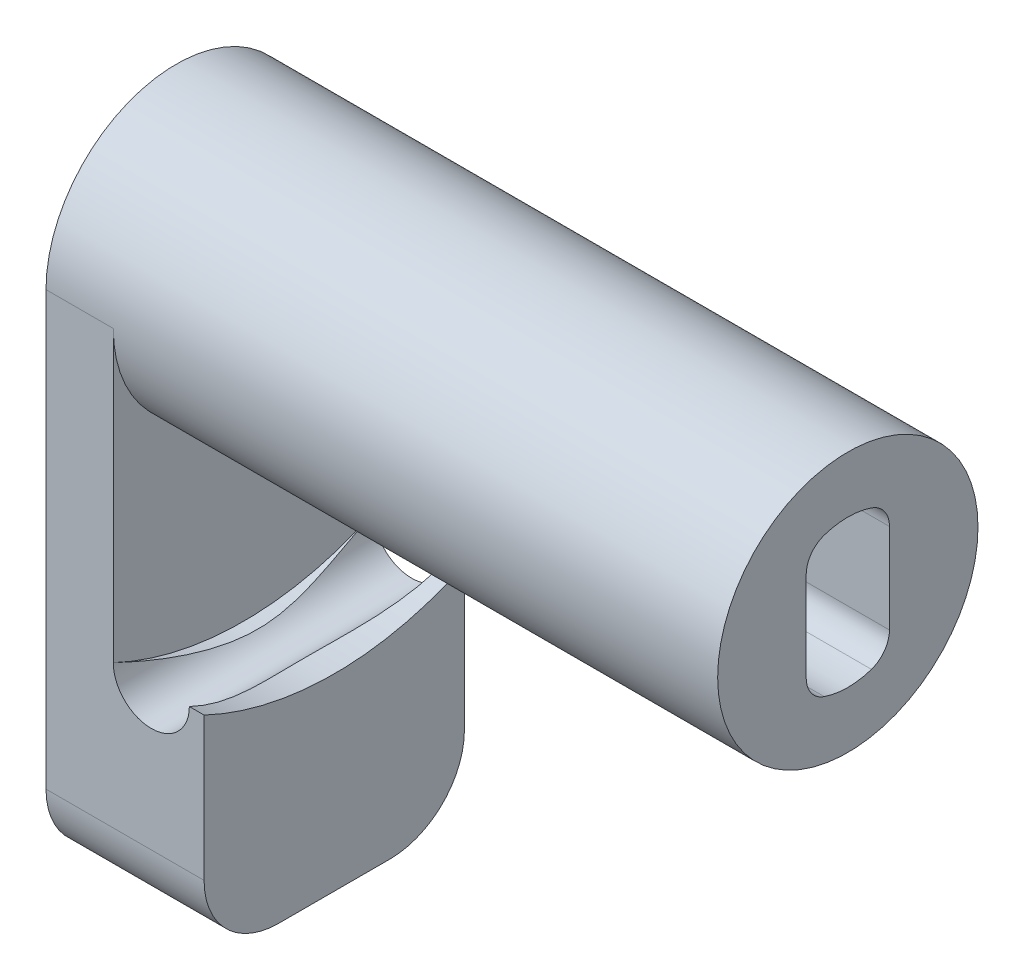
SolidWorks part; units mm, degrees
material "ABS"
ref_plane "Front Plane" through (0, 0, 0) normal (1, 0, 0) x (0, 1, 0)
ref_plane "Top Plane" through (0, 0, 0) normal (0, 0, 1) x (0, 1, 0)
ref_plane "Right Plane" through (0, 0, 0) normal (0, 1, 0) x (-1, 0, 0)
sketch "Sketch1" plane through (0, 0, 0) normal (1, 0, 0) x (0, 1, 0)
  circle A2 centre (0, 0) radius 8.7376
  dimension "D3" = 17.4752
extrude "Boss-Extrude1" add sketch "Sketch1" along normal blind 45.085 contours A2 region at (0, 0, 0)
sketch "Sketch10" plane through (0, 0, 0) normal (-1, 0, 0) x (0, -1, 0)
  line L0 (0, 8.7376) -> (34.036, 8.7376)
  line L2 (34.036, 8.7376) -> (34.036, -8.7376)
  line L3 (34.036, -8.7376) -> (0, -8.7376)
  circle A0 centre (0, 0) radius 8.7376 construction
  arc A2 (0, 8.7376) -> (0, -8.7376) centre (0, 0) cw
  point P2 (34.036, 0)
  dimension "D1" = 34.036
extrude "Boss-Extrude3" add sketch "Sketch10" against normal blind 4.516 contours L0 A2 L3 L2 region at (0, -20.3793, 0)
fillet "Fillet2" radius 5 2 edges at (2.258, -34.036, 8.7376) (2.258, -34.036, -8.7376)
sketch "Sketch14" [suppressed] plane through (0, 0, 0) normal (-1, 0, 0) x (0, 0, 1)
  line L0 (0.5115, -3.4237) -> (0.3944, -4.0089)
  line L1 (0, 0) -> (0, -4.064) construction
  line L2 (0, 0) -> (0.5606, -3.4335) construction
  line L3 (0.6039, -3.4087) -> (0.9011, -3.9262)
  line L4 (-0.6903, -3.3922) -> (-1.0005, -3.9021)
  line L5 (-0.5983, -3.4096) -> (-0.4961, -3.9976)
  line L6 (-1.8089, -2.9515) -> (-2.2748, -3.3245)
  line L7 (-1.7284, -2.9994) -> (-1.8334, -3.5869)
  line L8 (-2.7093, -2.1549) -> (-3.2746, -2.346)
  line L9 (-2.65, -2.2273) -> (-2.9496, -2.7435)
  line L10 (-3.2829, -1.0983) -> (-3.8795, -1.0846)
  line L11 (-3.252, -1.1867) -> (-3.7101, -1.5692)
  line L12 (-3.4605, 0.0907) -> (-4.0165, 0.3077)
  line L13 (-3.4617, -0.0029) -> (-4.023, -0.2057)
  line L14 (-3.2208, 1.2689) -> (-3.669, 1.6629)
  line L15 (-3.2539, 1.1813) -> (-3.8507, 1.1827)
  line L16 (-2.5926, 2.2939) -> (-2.879, 2.8175)
  line L17 (-2.6537, 2.223) -> (-3.214, 2.4284)
  line L18 (-1.6517, 3.0423) -> (-1.7417, 3.6323)
  line L19 (-1.7333, 2.9965) -> (-2.1896, 3.3812)
  line L20 (-0.5115, 3.4237) -> (-0.3944, 4.0089)
  line L21 (-0.6039, 3.4087) -> (-0.9011, 3.9262)
  line L22 (0.6903, 3.3922) -> (1.0005, 3.9021)
  line L23 (0.5983, 3.4096) -> (0.4961, 3.9976)
  line L24 (1.8089, 2.9515) -> (2.2748, 3.3245)
  line L25 (1.7284, 2.9994) -> (1.8334, 3.5869)
  line L26 (2.7093, 2.1549) -> (3.2746, 2.346)
  line L27 (2.65, 2.2273) -> (2.9496, 2.7435)
  line L28 (3.2829, 1.0983) -> (3.8795, 1.0846)
  line L29 (3.252, 1.1867) -> (3.7101, 1.5692)
  line L30 (3.4605, -0.0907) -> (4.0165, -0.3077)
  line L31 (3.4617, 0.0029) -> (4.023, 0.2057)
  line L32 (3.2208, -1.2689) -> (3.669, -1.6629)
  line L33 (3.2539, -1.1813) -> (3.8507, -1.1827)
  line L34 (2.5926, -2.2939) -> (2.879, -2.8175)
  line L35 (2.6537, -2.223) -> (3.214, -2.4284)
  line L36 (1.6517, -3.0423) -> (1.7417, -3.6323)
  line L37 (1.7333, -2.9965) -> (2.1896, -3.3812)
  line L38 (-0.1032, -4.0627) -> (0, -4.064)
  line L39 (-1.4865, -3.7824) -> (-1.39, -3.8189)
  line L40 (-2.6905, -3.0459) -> (-2.6123, -3.1132)
  line L41 (-3.5195, -2.032) -> (-3.57, -1.942)
  line L42 (-4.0023, -0.7057) -> (-4.0189, -0.6039)
  line L43 (-4.0023, 0.7057) -> (-3.9831, 0.8071)
  line L44 (-3.5195, 2.032) -> (-3.4668, 2.1207)
  line L45 (-2.6123, 3.1132) -> (-2.5324, 3.1785)
  line L46 (-1.39, 3.8189) -> (-1.2926, 3.853)
  line L47 (0, 4.064) -> (0.1032, 4.0627)
  line L48 (1.39, 3.8189) -> (1.4865, 3.7824)
  line L49 (2.6123, 3.1132) -> (2.6905, 3.0459)
  line L50 (3.5195, 2.032) -> (3.57, 1.942)
  line L51 (4.0023, 0.7057) -> (4.0189, 0.6039)
  line L52 (4.0023, -0.7057) -> (3.9831, -0.8071)
  line L53 (3.5195, -2.032) -> (3.4668, -2.1207)
  line L54 (2.6123, -3.1132) -> (2.5324, -3.1785)
  line L55 (1.39, -3.8189) -> (1.2926, -3.853)
  arc A0 (0.3497, -4.0489) -> (0, -4.064) centre (0, 0) cw
  arc A1 (0.3497, -4.0489) -> (0.3944, -4.0089) centre (0.3454, -3.9991) ccw
  arc A2 (0.5115, -3.4237) -> (0.6039, -3.4087) centre (0.5606, -3.4335) cw
  arc A3 (0.4203, -4.0631) -> (0.3944, -4.0089) centre (0.4434, -4.0187) cw
  arc A4 (0.4203, -4.0631) -> (0.7372, -4.2116) centre (2.3016, -0.4608) ccw
  arc A6 (0.9562, -3.9499) -> (0.9011, -3.9262) centre (0.9445, -3.9013) cw
  arc A7 (0.9562, -3.9499) -> (1.2926, -3.853) centre (0, 0) ccw
  arc A8 (-1.0562, -3.9243) -> (-1.39, -3.8189) centre (0, 0) cw
  arc A9 (-1.0562, -3.9243) -> (-1.0005, -3.9021) centre (-1.0432, -3.8761) ccw
  arc A10 (-0.6903, -3.3922) -> (-0.5983, -3.4096) centre (-0.6476, -3.4182) cw
  arc A11 (-0.4524, -4.0387) -> (-0.4961, -3.9976) centre (-0.4468, -3.9891) cw
  arc A12 (-0.4524, -4.0387) -> (-0.1032, -4.0627) centre (0, 0) ccw
  arc A13 (-2.3347, -3.3264) -> (-2.6123, -3.1132) centre (0, 0) cw
  arc A14 (-2.3347, -3.3264) -> (-2.2748, -3.3245) centre (-2.306, -3.2855) ccw
  arc A15 (-1.8089, -2.9515) -> (-1.7284, -2.9994) centre (-1.7776, -2.9906) cw
  arc A16 (-1.8064, -3.6405) -> (-1.8334, -3.5869) centre (-1.7842, -3.5957) cw
  arc A17 (-1.8064, -3.6405) -> (-1.4865, -3.7824) centre (0, 0) ccw
  arc A18 (-3.3316, -2.3273) -> (-3.5195, -2.032) centre (0, 0) cw
  arc A19 (-3.3316, -2.3273) -> (-3.2746, -2.346) centre (-3.2906, -2.2987) ccw
  arc A20 (-2.7093, -2.1549) -> (-2.65, -2.2273) centre (-2.6933, -2.2022) cw
  arc A21 (-2.9426, -2.8031) -> (-2.9496, -2.7435) centre (-2.9064, -2.7686) cw
  arc A22 (-2.9426, -2.8031) -> (-2.6905, -3.0459) centre (0, 0) ccw
  arc A23 (-3.9267, -1.0475) -> (-4.0023, -0.7057) centre (0, 0) cw
  arc A24 (-3.9267, -1.0475) -> (-3.8795, -1.0846) centre (-3.8784, -1.0346) ccw
  arc A25 (-3.2829, -1.0983) -> (-3.252, -1.1867) centre (-3.284, -1.1483) cw
  arc A26 (-3.7238, -1.6276) -> (-3.7101, -1.5692) centre (-3.678, -1.6076) cw
  arc A27 (-3.7238, -1.6276) -> (-3.57, -1.942) centre (0, 0) ccw
  arc A28 (-4.0481, 0.3587) -> (-4.0023, 0.7057) centre (0, 0) cw
  arc A29 (-4.0481, 0.3587) -> (-4.0165, 0.3077) centre (-3.9983, 0.3543) ccw
  arc A30 (-3.4605, 0.0907) -> (-3.4617, -0.0029) centre (-3.4787, 0.0442) cw
  arc A31 (-4.0559, -0.2558) -> (-4.023, -0.2057) centre (-4.006, -0.2527) cw
  arc A32 (-4.0559, -0.2558) -> (-4.0189, -0.6039) centre (0, 0) ccw
  arc A33 (-3.6813, 1.7216) -> (-3.5195, 2.032) centre (0, 0) cw
  arc A34 (-3.6813, 1.7216) -> (-3.669, 1.6629) centre (-3.636, 1.7005) ccw
  arc A35 (-3.2208, 1.2689) -> (-3.2539, 1.1813) centre (-3.2538, 1.2313) cw
  arc A36 (-3.8988, 1.1468) -> (-3.8507, 1.1827) centre (-3.8509, 1.1327) cw
  arc A37 (-3.8988, 1.1468) -> (-3.9831, 0.8071) centre (0, 0) ccw
  arc A38 (-2.8705, 2.8769) -> (-2.6123, 3.1132) centre (0, 0) cw
  arc A39 (-2.8705, 2.8769) -> (-2.879, 2.8175) centre (-2.8352, 2.8415) ccw
  arc A40 (-2.5926, 2.2939) -> (-2.6537, 2.223) centre (-2.6365, 2.2699) cw
  arc A41 (-3.2715, 2.4111) -> (-3.214, 2.4284) centre (-3.2312, 2.3815) cw
  arc A42 (-3.2715, 2.4111) -> (-3.4668, 2.1207) centre (0, 0) ccw
  arc A43 (-1.7134, 3.6852) -> (-1.39, 3.8189) centre (0, 0) cw
  arc A44 (-1.7134, 3.6852) -> (-1.7417, 3.6323) centre (-1.6923, 3.6398) ccw
  arc A45 (-1.6517, 3.0423) -> (-1.7333, 2.9965) centre (-1.7011, 3.0348) cw
  arc A46 (-2.2495, 3.3846) -> (-2.1896, 3.3812) centre (-2.2218, 3.343) cw
  arc A47 (-2.2495, 3.3846) -> (-2.5324, 3.1785) centre (0, 0) ccw
  arc A48 (-0.3497, 4.0489) -> (0, 4.064) centre (0, 0) cw
  arc A49 (-0.3497, 4.0489) -> (-0.3944, 4.0089) centre (-0.3454, 3.9991) ccw
  arc A50 (-0.5115, 3.4237) -> (-0.6039, 3.4087) centre (-0.5606, 3.4335) cw
  arc A51 (-0.9562, 3.9499) -> (-0.9011, 3.9262) centre (-0.9445, 3.9013) cw
  arc A52 (-0.9562, 3.9499) -> (-1.2926, 3.853) centre (0, 0) ccw
  arc A53 (1.0562, 3.9243) -> (1.39, 3.8189) centre (0, 0) cw
  arc A54 (1.0562, 3.9243) -> (1.0005, 3.9021) centre (1.0432, 3.8761) ccw
  arc A55 (0.6903, 3.3922) -> (0.5983, 3.4096) centre (0.6476, 3.4182) cw
  arc A56 (0.4524, 4.0387) -> (0.4961, 3.9976) centre (0.4468, 3.9891) cw
  arc A57 (0.4524, 4.0387) -> (0.1032, 4.0627) centre (0, 0) ccw
  arc A58 (2.3347, 3.3264) -> (2.6123, 3.1132) centre (0, 0) cw
  arc A59 (2.3347, 3.3264) -> (2.2748, 3.3245) centre (2.306, 3.2855) ccw
  arc A60 (1.8089, 2.9515) -> (1.7284, 2.9994) centre (1.7776, 2.9906) cw
  arc A61 (1.8064, 3.6405) -> (1.8334, 3.5869) centre (1.7842, 3.5957) cw
  arc A62 (1.8064, 3.6405) -> (1.4865, 3.7824) centre (0, 0) ccw
  arc A63 (3.3316, 2.3273) -> (3.5195, 2.032) centre (0, 0) cw
  arc A64 (3.3316, 2.3273) -> (3.2746, 2.346) centre (3.2906, 2.2987) ccw
  arc A65 (2.7093, 2.1549) -> (2.65, 2.2273) centre (2.6933, 2.2022) cw
  arc A66 (2.9426, 2.8031) -> (2.9496, 2.7435) centre (2.9064, 2.7686) cw
  arc A67 (2.9426, 2.8031) -> (2.6905, 3.0459) centre (0, 0) ccw
  arc A68 (3.9267, 1.0475) -> (4.0023, 0.7057) centre (0, 0) cw
  arc A69 (3.9267, 1.0475) -> (3.8795, 1.0846) centre (3.8784, 1.0346) ccw
  arc A70 (3.2829, 1.0983) -> (3.252, 1.1867) centre (3.284, 1.1483) cw
  arc A71 (3.7238, 1.6276) -> (3.7101, 1.5692) centre (3.678, 1.6076) cw
  arc A72 (3.7238, 1.6276) -> (3.57, 1.942) centre (0, 0) ccw
  arc A73 (4.0481, -0.3587) -> (4.0023, -0.7057) centre (0, 0) cw
  arc A74 (4.0481, -0.3587) -> (4.0165, -0.3077) centre (3.9983, -0.3543) ccw
  arc A75 (3.4605, -0.0907) -> (3.4617, 0.0029) centre (3.4787, -0.0442) cw
  arc A76 (4.0559, 0.2558) -> (4.023, 0.2057) centre (4.006, 0.2527) cw
  arc A77 (4.0559, 0.2558) -> (4.0189, 0.6039) centre (0, 0) ccw
  arc A78 (3.6813, -1.7216) -> (3.5195, -2.032) centre (0, 0) cw
  arc A79 (3.6813, -1.7216) -> (3.669, -1.6629) centre (3.636, -1.7005) ccw
  arc A80 (3.2208, -1.2689) -> (3.2539, -1.1813) centre (3.2538, -1.2313) cw
  arc A81 (3.8988, -1.1468) -> (3.8507, -1.1827) centre (3.8509, -1.1327) cw
  arc A82 (3.8988, -1.1468) -> (3.9831, -0.8071) centre (0, 0) ccw
  arc A83 (2.8705, -2.8769) -> (2.6123, -3.1132) centre (0, 0) cw
  arc A84 (2.8705, -2.8769) -> (2.879, -2.8175) centre (2.8352, -2.8415) ccw
  arc A85 (2.5926, -2.2939) -> (2.6537, -2.223) centre (2.6365, -2.2699) cw
  arc A86 (3.2715, -2.4111) -> (3.214, -2.4284) centre (3.2312, -2.3815) cw
  arc A87 (3.2715, -2.4111) -> (3.4668, -2.1207) centre (0, 0) ccw
  arc A88 (1.7134, -3.6852) -> (1.39, -3.8189) centre (0, 0) cw
  arc A89 (1.7134, -3.6852) -> (1.7417, -3.6323) centre (1.6923, -3.6398) ccw
  arc A90 (1.6517, -3.0423) -> (1.7333, -2.9965) centre (1.7011, -3.0348) cw
  arc A91 (2.2495, -3.3846) -> (2.1896, -3.3812) centre (2.2218, -3.343) cw
  arc A92 (2.2495, -3.3846) -> (2.5324, -3.1785) centre (0, 0) ccw
  point P207 (0, 0)
  dimension "D1" = 4.064
  dimension "D2" = 0.05
  dimension "D3" = 0.05
  dimension "D4" = 0.04
  dimension "D5" = 18
  dimension "D6" = 0.5968
  dimension "D8" = 0.35
sketch "Sketch15" plane through (4.516, 0, 0) normal (1, 0, 0) x (0, 1, 0)
  line L4 (-18.7904, 8.7376) -> (-18.7904, -8.7376)
  line L10 (0, 8.7376) -> (-29.036, 8.7376)
  line L11 (-29.036, -8.7376) -> (0, -8.7376)
  line L12 (-18.7904, 8.7376) -> (-29.036, 8.7376)
  line L13 (-34.036, 3.7376) -> (-34.036, -3.7376)
  line L14 (-29.036, -8.7376) -> (-18.7904, -8.7376)
  line L15 (-34.036, 3.7376) -> (-34.036, -3.7376)
  arc A13 (-29.036, 8.7376) -> (-34.036, 3.7376) centre (-29.036, 3.7376) ccw
  arc A14 (-34.036, -3.7376) -> (-29.036, -8.7376) centre (-29.036, -3.7376) ccw
  arc A15 (0, 8.7376) -> (0, -8.7376) centre (0, 0) ccw
  arc A16 (-29.036, 8.7376) -> (-34.036, 3.7376) centre (-29.036, 3.7376) ccw
  arc A17 (-34.036, -3.7376) -> (-29.036, -8.7376) centre (-29.036, -3.7376) ccw
  line M2 (0, 8.7376) -> (-29.036, 8.7376)
  arc M3 (-29.036, 8.7376) -> (-34.036, 3.7376) centre (-29.036, 3.7376) ccw
  line M4 (-34.036, 3.7376) -> (-34.036, -3.7376)
  arc M5 (-34.036, -3.7376) -> (-29.036, -8.7376) centre (-29.036, -3.7376) ccw
  dimension "D1" = 0
extrude "Boss-Extrude4" add sketch "Sketch15" along normal blind 6.096 contours M2 M3 M4 M5 region at (4.516, -26.1402, 0)
sketch "Sketch21" plane through (10.612, 0, 0) normal (1, 0, 0) x (0, 1, 0)
  line L2 (-18.7904, -8.7376) -> (-18.7904, 8.7376)
  line L5 (-19.4254, -8.7376) -> (-18.7904, -8.7376)
  line L7 (-18.7904, 8.7376) -> (-18.7904, -8.7376) construction
  line L8 (-18.7904, -8.7376) -> (0, -8.7376) construction
  line L11 (-18.7904, 8.7376) -> (-29.036, 8.7376) construction
  line L14 (-18.7904, -8.7376) -> (-18.7904, 8.7376) construction
  line L20 (-18.7904, 8.7376) -> (-19.4254, 8.7376)
  arc A2 (-19.4254, -8.7376) -> (-19.4254, 8.7376) centre (-1.0799, 0) cw
  dimension "D4" = 20.32
  dimension "D2" = 0.635
  dimension "D3" = 0.635
extrude "Cut-Extrude8" cut sketch "Sketch21" against normal up to surface (6.096 mm away) contours A2 L2 region at (10.612, -19.8596, 0) up to face at (4.516, -11.5796, 0)
sketch "Sketch22" plane through (45.085, 0, 0) normal (1, 0, 0) x (0, 1, 0)
  line L7 (-4.0897, -2.794) -> (4.0897, 2.794) construction
  line L8 (-4.0897, 2.794) -> (4.0897, -2.794) construction
  line L11 (-4.0897, -2.794) -> (4.0897, -2.794)
  line L13 (-4.0897, 2.794) -> (4.0897, 2.794)
  line L15 (-4.0897, -2.794) -> (4.0897, 2.794) construction
  line L16 (-4.0897, 2.794) -> (4.0897, -2.794) construction
  arc A3 (-4.0897, 2.794) -> (-4.0897, -2.794) centre (0, 0) ccw
  arc A4 (4.0897, -2.794) -> (4.0897, 2.794) centre (0, 0) ccw
  dimension "D2" = 9.906
  dimension "D3" = 5.588
extrude "Cut-Extrude10" cut sketch "Sketch22" against normal blind 12.192
fillet "Fillet11" radius 1.778 4 edges at (38.989, 4.0897, -2.794) (38.989, 4.0897, 2.794) (38.989, -4.0897, -2.794) (38.989, -4.0897, 2.794)
sketch "Sketch25" plane through (0, 0, -8.7376) normal (0, 0, -1) x (1, 0, 0)
  line L3 (4.516, 19.4254) -> (4.516, 0) construction
  line L4 (4.516, 19.4254) -> (10.612, 19.4254) construction
  circle A0 centre (7.0687, 19.4254) radius 2.5527
  dimension "D1" = 5.1054
extrude "Cut-Extrude14" cut sketch "Sketch25" against normal through all
sketch "Sketch26" plane through (0, 0, 0) normal (-1, 0, 0) x (0, -1, 0)
  line L1 (3.6846, 1.7145) -> (7.1771, 1.7145)
  line L2 (3.6846, 1.7145) -> (3.6846, -1.7145) construction
  line L3 (3.6846, -1.7145) -> (7.1771, -1.7145)
  line L4 (7.1771, 1.7145) -> (7.1771, -1.7145)
  arc A0 (3.6846, 1.7145) -> (3.6846, -1.7145) centre (0, 0) ccw
  dimension "D1" = 8.128
  dimension "D2" = 3.429
  dimension "D3" = 3.4925
extrude "Cut-Extrude15" cut sketch "Sketch26" against normal blind 17.78
fillet "Fillet12" radius 1.5875 4 edges at (8.89, -3.6846, 1.7145) (8.89, -7.1771, 1.7145) (8.89, -3.6846, -1.7145) (8.89, -7.1771, -1.7145)
